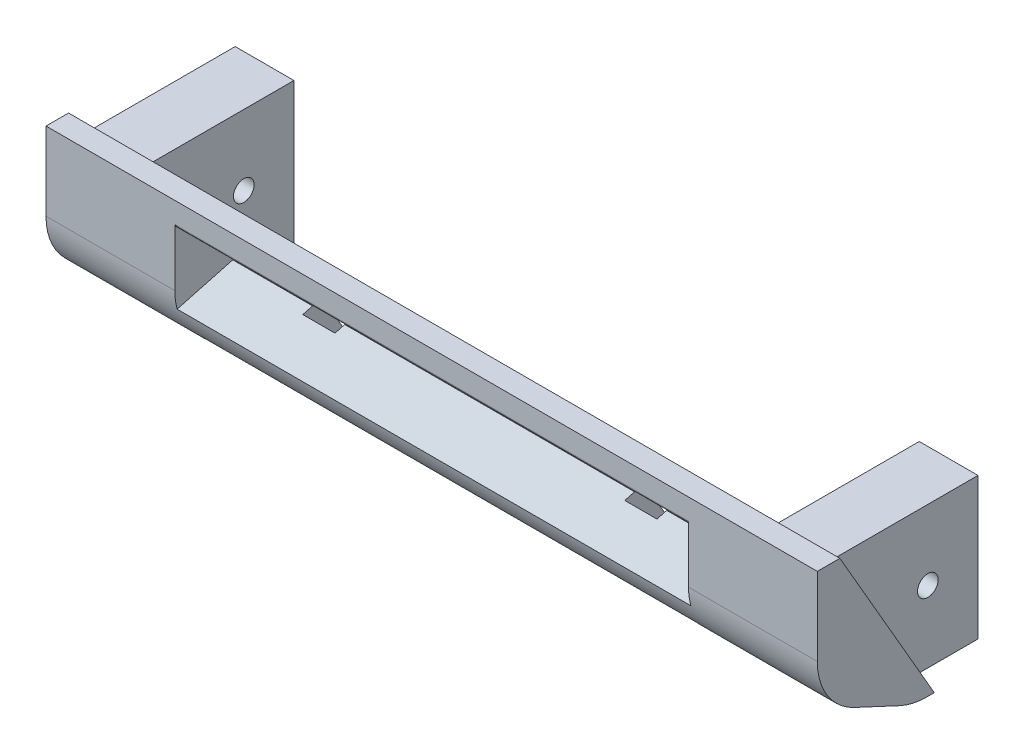
SolidWorks part; units mm, degrees
ref_plane "Front Plane" through (0, 0, 0) normal (0, 0, 1) x (1, 0, 0)
ref_plane "Top Plane" through (0, 0, 0) normal (0, 1, 0) x (1, 0, 0)
ref_plane "Right Plane" through (0, 0, 0) normal (1, 0, 0) x (0, 0, -1)
sketch "Sketch1" plane through (0, 0, 0) normal (1, 0, 0) x (0, 0, -1)
  line L0 (0, 0) -> (-29.3294, 50.8)
  line L1 (0, 0) -> (50, 0) construction
  line L2 (-29.3294, 50.8) -> (-36.3294, 50.8)
  line L3 (-36.3294, 13.8) -> (-6.7352, 0)
  line L6 (-36.3294, 50.8) -> (-36.3294, 13.8)
  line L7 (-6.7352, 0) -> (0, 0)
  line L8 (0, 0) -> (0, 21.8413) construction
  dimension "D1" = 65
  dimension "D2" = 6.7352
  dimension "D3" = 37
extrude "Boss-Extrude2" add sketch "Sketch1" along normal mid plane 239.55
sketch "Sketch2" plane through (0, 0, 0) normal (0, 0, 1) x (1, 0, 0)
  line L0 (0, 0) -> (0, 50.8) construction
  line L5 (115.75, 47.625) -> (96.7, 47.625) construction
  line L6 (115.75, 47.625) -> (115.75, 2.825) construction
  line L11 (115.75, 2.825) -> (96.7, 2.825) construction
  line L12 (96.7, 47.625) -> (96.7, 2.825) construction
  line L14 (115.35, 47.225) -> (115.35, 3.225)
  line L15 (115.35, 3.225) -> (97.1, 3.225)
  line L28 (97.1, 47.225) -> (97.1, 3.225)
  line L29 (115.35, 47.225) -> (97.1, 47.225)
  line L30 (-96.7, 47.625) -> (-96.7, 2.825) construction
  line L31 (-115.75, 2.825) -> (-96.7, 2.825) construction
  line L32 (-115.75, 47.625) -> (-115.75, 2.825) construction
  line L33 (-115.75, 47.625) -> (-96.7, 47.625) construction
  line L34 (-115.35, 47.225) -> (-97.1, 47.225)
  line L35 (-97.1, 47.225) -> (-97.1, 3.225)
  line L36 (-115.35, 3.225) -> (-97.1, 3.225)
  line L37 (-115.35, 47.225) -> (-115.35, 3.225)
  line L40 (119.775, 50.8) -> (-119.775, 50.8) construction
  line L41 (119.775, 0) -> (119.775, 50.8) construction
  dimension "D2" = 19.05
  dimension "D4" = 3.175
  dimension "D7" = 4.025
  dimension "D1" = 193.4
  dimension "D3" = 44
  dimension "D5" = 0.4
extrude "Boss-Extrude1" add sketch "Sketch2" along normal up to surface and the other way blind 18 up to face at (0, 25.4, 14.6647)
sketch "Sketch12" plane through (0, -2.5797, 1.2029) normal (0, -0.9063, 0.4226) x (1, 0, 0)
  line L0 (-95.2, -603.0139) -> (-95.2, 0.9459) construction
  line L1 (-95.2, -603.0139) -> (-95.2, 0.9459) construction
  line L2 (119.775, 0) -> (-119.775, 0) construction
  line L3 (70, 15) -> (-70, 15)
  line L4 (70, 15) -> (70, 0)
  line L5 (70, 0) -> (-70, 0)
  line L6 (-70, 15) -> (-70, 0)
  line L7 (70, 15) -> (-70, 0) construction
  line L8 (70, 0) -> (-70, 15) construction
  line L10 (95.2, 44.3946) -> (-95.2, 44.3946)
  line L11 (95.2, 44.3946) -> (95.2, 19.3946)
  line L12 (95.2, 19.3946) -> (-95.2, 19.3946)
  line L13 (-95.2, 44.3946) -> (-95.2, 19.3946)
  line L14 (95.2, 44.3946) -> (-95.2, 19.3946) construction
  line L15 (95.2, 19.3946) -> (-95.2, 44.3946) construction
  line L16 (-120.6, 54.3946) -> (120.6, 54.3946) construction
  point P2 (0, 7.5)
  point P11 (0, 31.8946)
  dimension "D1" = 15
  dimension "D2" = 140
  dimension "D3" = 10
  dimension "D4" = 25
  dimension "D5" = 4.3946
extrude "Cut-Extrude4" [suppressed] cut sketch "Sketch12" against normal up to next
hole_wizard "M6 Clearance Hole1" positions "Sketch11" profile "Sketch10" hole size "M6" standard "ANSI Metric" end condition through all
sketch "Sketch11" plane through (115.35, 0, 0) normal (1, 0, 0) x (0, 0, -1)
  point P0 (2.4206, 25.4)
sketch "Sketch10" plane through (115.35, 25.4, -2.4206) normal (0, 1, 0) x (0, 0, -1)
  line L0 (0, 0) -> (0, 235.125)
  line L1 (0, 235.125) -> (3.2, 235.125)
  line L2 (3.2, 235.125) -> (3.2, 0)
  line L5 (3.2, 0) -> (0, 0)
  line L11 (0, -6.35) -> (0, 107.95) construction
  dimension "Thru Hole Dia." = 6.4
  dimension "Thru Hole Depth" = 235.125
sketch "Sketch13" plane through (0, 0, 0) normal (0, 0, 1) x (1, 0, 0)
  line L0 (119.775, 0) -> (-119.775, 0) construction
  line L1 (-76.872, 13.5) -> (76.872, 13.5)
  line L2 (-76.872, 13.5) -> (-76.872, 0)
  line L3 (-76.872, 0) -> (76.872, 0)
  line L4 (76.872, 13.5) -> (76.872, 0)
  line L5 (-76.872, 13.5) -> (76.872, 0) construction
  line L6 (-76.872, 0) -> (76.872, 13.5) construction
  line L7 (119.775, 50.8) -> (-119.775, 50.8) construction
  line L8 (-79.775, 25.8) -> (79.775, 25.8)
  line L9 (-79.775, 25.8) -> (-79.775, 40.8)
  line L10 (-79.775, 40.8) -> (79.775, 40.8)
  line L11 (79.775, 25.8) -> (79.775, 40.8)
  line L12 (-79.775, 25.8) -> (79.775, 40.8) construction
  line L13 (-79.775, 40.8) -> (79.775, 25.8) construction
  line L14 (-119.775, 50.8) -> (-119.775, 13.8) construction
  line L15 (0, 50.8) -> (0, -69.7748) construction
  point P0 (0, 6.75)
  point P7 (0, 33.3)
  dimension "D1" = 13.5
  dimension "D2" = 10
  dimension "D3" = 40
  dimension "D4" = 15
extrude "Cut-Extrude6" cut sketch "Sketch13" against normal through all both and the other way through all
chamfer "Chamfer5" distance 18 angle 15 1 edges at (0, 40.8, 23.5559) first distance on face at (0, 40.8, 29.9426)
chamfer "Chamfer6" distance 18 angle 15 1 edges at (0, 25.8, 36.3294) first distance on face at (0, 25.8, 25.6125)
sketch "Sketch14" plane through (0, 13.5, 0) normal (0, -1, 0) x (1, 0, 0)
  line L0 (-49.8748, 11.7942) -> (50.6947, 11.7942) construction
  line L1 (76.872, 7.7942) -> (-76.872, 7.7942) construction
  line L2 (47.1947, 15.7942) -> (54.1947, 15.7942)
  line L3 (47.1947, 15.7942) -> (47.1947, 7.7942)
  line L4 (47.1947, 7.7942) -> (54.1947, 7.7942)
  line L5 (54.1947, 15.7942) -> (54.1947, 7.7942)
  line L6 (47.1947, 15.7942) -> (54.1947, 7.7942) construction
  line L7 (47.1947, 7.7942) -> (54.1947, 15.7942) construction
  line L9 (-53.3748, 15.7942) -> (-46.3748, 15.7942)
  line L10 (-53.3748, 15.7942) -> (-53.3748, 7.7942)
  line L11 (-53.3748, 7.7942) -> (-46.3748, 7.7942)
  line L12 (-46.3748, 15.7942) -> (-46.3748, 7.7942)
  line L13 (-53.3748, 15.7942) -> (-46.3748, 7.7942) construction
  line L14 (-53.3748, 7.7942) -> (-46.3748, 15.7942) construction
  point P0 (50.6947, 11.7942)
  point P3 (0.4099, 11.7942)
  dimension "D1" = 7
  dimension "D2" = 7
  dimension "D3" = 8
ref_plane "Plane2" through (0, 13.5, 7.7942) normal (0, 0.866, 0.5) x (-1, 0, 0)
sketch "Sketch15" plane through (0, 13.5, 7.7942) normal (0, 0.866, 0.5) x (-1, 0, 0)
  line L0 (-50, 3) -> (50, 3) construction
  line L1 (-76.872, 0) -> (76.872, 0) construction
  line L2 (-45, 6) -> (-55, 6)
  line L3 (-45, 6) -> (-45, 0)
  line L4 (-45, 0) -> (-55, 0)
  line L5 (-55, 6) -> (-55, 0)
  line L6 (-45, 6) -> (-55, 0) construction
  line L7 (-45, 0) -> (-55, 6) construction
  line L9 (45, 6) -> (55, 6)
  line L10 (45, 6) -> (45, 0)
  line L11 (45, 0) -> (55, 0)
  line L12 (55, 6) -> (55, 0)
  line L13 (45, 6) -> (55, 0) construction
  line L14 (45, 0) -> (55, 6) construction
  point P3 (0, 3)
  dimension "D1" = 10
  dimension "D2" = 10
  dimension "D3" = 6
  dimension "D4" = 100
extrude "Cut-Extrude8" cut sketch "Sketch15" along normal up to surface (16.7306 mm away) up to face at (0, 23.3885, 27.3294)
fillet "Fillet1" radius 4 1 edges at (0, 42.2004, 36.3294) second distance 1 first distance on face at (0, 43.5887, 31.1484)
fillet "Fillet2" radius 20 2 edges at (-98.3235, 0, 6.7352) (98.3235, 0, 6.7352)
fillet "Fillet3" radius 20 1 edges at (0, 13.8, 36.3294)
sketch "Sketch16" plane through (0, 13.5, 0) normal (0, -1, 0) x (1, 0, 0)
  line L0 (0, 0) -> (0, 36.3294) construction
  line L1 (-79.775, 36.3294) -> (79.775, 36.3294) construction
  line L2 (-62.5, 27.5) -> (-69.5, 20.5) construction
  line L3 (62.5, 20.5) -> (69.5, 20.5)
  line L4 (62.5, 20.5) -> (62.5, 27.5)
  line L5 (62.5, 27.5) -> (69.5, 27.5)
  line L6 (69.5, 20.5) -> (69.5, 27.5)
  line L7 (62.5, 20.5) -> (69.5, 27.5) construction
  line L8 (62.5, 27.5) -> (69.5, 20.5) construction
  line L9 (-62.5, 20.5) -> (-69.5, 27.5) construction
  line L10 (-69.5, 20.5) -> (-69.5, 27.5)
  line L11 (-62.5, 27.5) -> (-69.5, 27.5)
  line L12 (-62.5, 20.5) -> (-62.5, 27.5)
  line L13 (-62.5, 20.5) -> (-69.5, 20.5)
  point P9 (66, 24)
  point P14 (-66, 24)
  dimension "D1" = 7
  dimension "D2" = 125
  dimension "D3" = 20.5
equation "\"D1@Sketch2\"=187.05mm+0.25in"
equation "\"RailSpacing\"= 188.75mm"
equation "\"D1@Boss-Extrude2\"=\"RailSpacing\"+2in"
